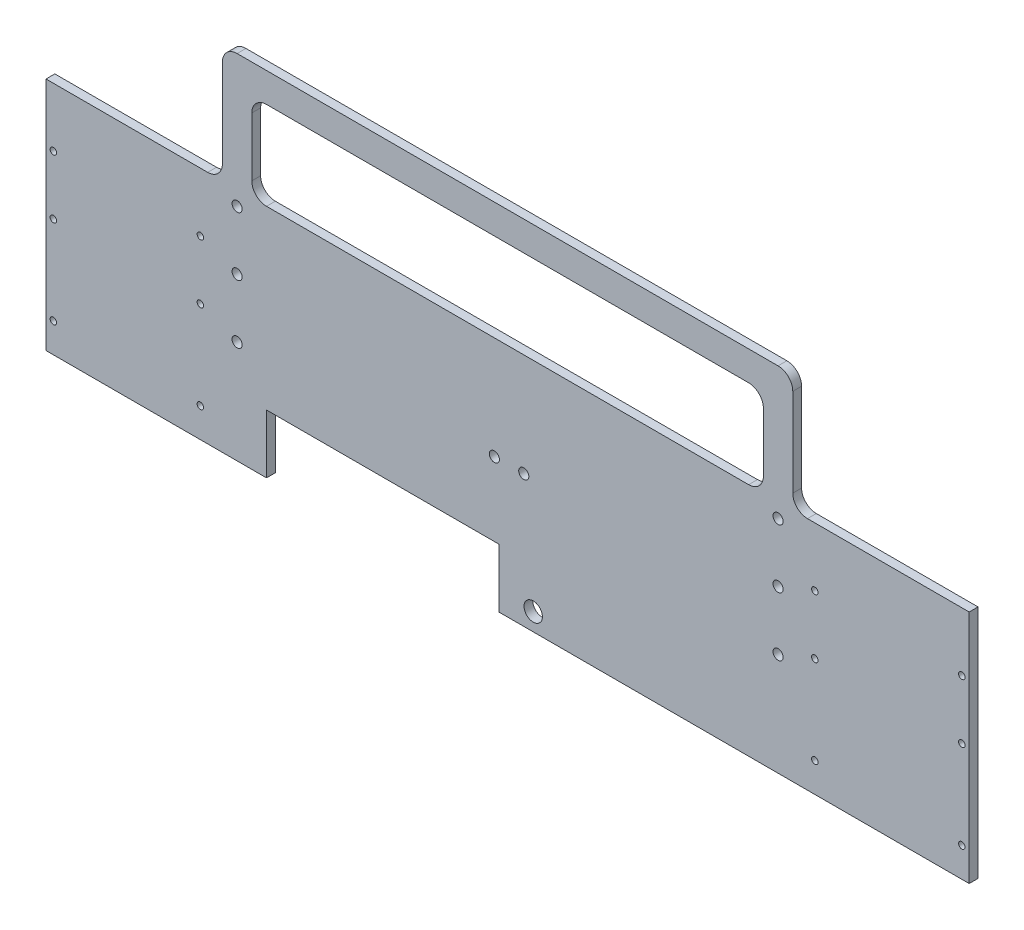
SolidWorks part; units mm, degrees
material "6061-T6 (SS)"
ref_plane "Front Plane" through (0, 0, 0) normal (0, 0, 1) x (1, 0, 0)
ref_plane "Top Plane" through (0, 0, 0) normal (0, 1, 0) x (1, 0, 0)
ref_plane "Right Plane" through (0, 0, 0) normal (1, 0, 0) x (0, 0, -1)
sketch "Sketch1" plane through (0, 0, 0) normal (0, 0, 1) x (1, 0, 0)
  line L1 (-199.39, 50.8) -> (199.39, 50.8)
  line L2 (-199.39, 50.8) -> (-199.39, -50.8)
  line L3 (-199.39, -50.8) -> (199.39, -50.8)
  line L4 (199.39, 50.8) -> (199.39, -50.8)
  line L5 (-199.39, 50.8) -> (199.39, -50.8) construction
  line L6 (-199.39, -50.8) -> (199.39, 50.8) construction
  point P0 (0, 0)
  dimension "D1" = 101.6
  dimension "D2" = 398.78
extrude "Boss-Extrude1" add sketch "Sketch1" along normal blind 3.81
sketch "Sketch2" plane through (0, 0, 3.81) normal (0, 0, 1) x (1, 0, 0)
  line L0 (199.39, -50.8) -> (199.39, 50.8) construction
  line L1 (-91.44, 27.94) -> (91.44, 27.94) construction
  line L2 (-91.44, 27.94) -> (-91.44, -27.94) construction
  line L3 (-91.44, -27.94) -> (91.44, -27.94) construction
  line L4 (91.44, 27.94) -> (91.44, -27.94) construction
  line L5 (-91.44, 27.94) -> (91.44, -27.94) construction
  line L6 (-91.44, -27.94) -> (91.44, 27.94) construction
  line L7 (194.818, -35.56) -> (-194.818, -35.56) construction
  line L8 (194.818, -35.56) -> (194.818, 1.27) construction
  line L9 (194.818, 1.27) -> (-194.818, 1.27) construction
  line L10 (-194.818, -35.56) -> (-194.818, 1.27) construction
  line L11 (194.818, -35.56) -> (-194.818, 1.27) construction
  line L12 (194.818, 1.27) -> (-194.818, -35.56) construction
  line L13 (-199.39, -50.8) -> (199.39, -50.8) construction
  point P0 (0, 0)
  point P6 (0, -17.145)
  point P13 (91.44, 0)
  point P19 (-91.44, 0)
  dimension "D1" = 182.88
  dimension "D2" = 55.88
  dimension "D3" = 4.572
  dimension "D4" = 36.83
  dimension "D5" = 15.24
sketch "Sketch10" plane through (0, 0, 3.81) normal (0, 0, 1) x (1, 0, 0)
  line L0 (199.39, 50.8) -> (-199.39, 50.8) construction
  line L1 (-123.19, 50.8) -> (-110.49, 50.8)
  line L2 (-123.19, 50.8) -> (-123.19, 101.6)
  line L3 (-123.19, 101.6) -> (-114.3, 101.6)
  line L4 (-110.49, 50.8) -> (-110.49, 88.9)
  line L5 (-199.39, 50.8) -> (-199.39, -50.8) construction
  line L6 (-123.19, 101.6) -> (123.19, 101.6)
  line L7 (-123.19, 101.6) -> (-123.19, 96.683)
  line L8 (-110.49, 88.9) -> (110.49, 88.9)
  line L9 (0, 101.6) -> (0, 88.9)
  line L10 (110.49, 50.8) -> (110.49, 88.9)
  line L11 (123.19, 50.8) -> (110.49, 50.8)
  line L12 (123.19, 50.8) -> (123.19, 101.6)
  line M12 (199.39, 50.8) -> (-199.39, 50.8)
  dimension "D1" = 12.7
  dimension "D2" = 12.7
  dimension "D3" = 123.19
  dimension "D4" = 76.2
  dimension "D5" = 50.8
extrude "Boss-Extrude2" add sketch "Sketch10" against normal blind 3.81 contours L9 L6 L3 L2 L4 L8 M12 | L12 L6 L9 L8 L10 M12 region at (-74.645, 89.25, 3.81) region at (74.645, 89.25, 3.81)
fillet "Fillet1" radius 6.35 8 edges at (123.19, 101.6, 1.905) (-123.19, 101.6, 1.905) (-123.19, 50.8, 1.905) (123.19, 50.8, 1.905) (110.49, 88.9, 1.905) (110.49, 50.8, 1.905) (-110.49, 50.8, 1.905) (-110.49, 88.9, 1.905)
sketch "Sketch9" plane through (0, 0, 3.81) normal (0, 0, 1) x (1, 0, 0)
  line L103 (-199.39, -50.8) -> (199.39, -50.8) construction
  point P113 (0, -50.8)
sketch "Sketch11" plane through (0, 0, 3.81) normal (0, 0, 1) x (1, 0, 0)
  line L0 (-199.39, -50.8) -> (199.39, -50.8) construction
  line L1 (-104.14, -50.8) -> (-3.81, -50.8)
  line L2 (-104.14, -50.8) -> (-104.14, -25.4)
  line L3 (-104.14, -25.4) -> (-3.81, -25.4)
  line L4 (-3.81, -50.8) -> (-3.81, -25.4)
  line L5 (-199.39, 50.8) -> (-199.39, -50.8) construction
  line L6 (199.39, -50.8) -> (199.39, 50.8) construction
  dimension "D1" = 25.4
  dimension "D2" = 95.25
  dimension "D3" = 203.2
extrude "Cut-Extrude1" cut sketch "Sketch11" against normal through all
sketch "Sketch12" plane through (0, 0, 3.81) normal (0, 0, 1) x (1, 0, 0)
  line L0 (-3.81, -50.8) -> (-3.81, -25.4) construction
  line L1 (-3.81, -50.8) -> (199.39, -50.8) construction
  point P0 (11.0749, -43.18)
  dimension "D1" = 14.8849
  dimension "D2" = 7.62
hole_wizard "5/16 (0.3125) Diameter Hole1" positions "Sketch13" profile "Sketch14" hole size "5/16" standard "ANSI Inch" end condition through all
sketch "Sketch13" plane through (0, 0, 3.81) normal (0, 0, 1) x (1, 0, 0)
  point P0 (11.0749, -43.18)
sketch "Sketch14" plane through (11.0749, -43.18, 3.81) normal (1, 0, 0) x (0, -1, 0)
  line L0 (0, 0) -> (0, 3.81)
  line L1 (0, 3.81) -> (3.9687, 3.81)
  line L2 (3.9687, 3.81) -> (3.9687, 0)
  line L5 (3.9687, 0) -> (0, 0)
  line L11 (0, -6.35) -> (0, 107.95) construction
  dimension "Thru Hole Dia." = 7.9375
  dimension "Thru Hole Depth" = 3.81
sketch "Sketch15" plane through (0, 0, 3.81) normal (0, 0, 1) x (1, 0, 0)
  line L0 (104.14, 50.8) -> (-104.14, 50.8) construction
  line L1 (-199.39, 50.8) -> (-199.39, -50.8) construction
  line L3 (199.39, -50.8) -> (199.39, 50.8) construction
  point P0 (-116.84, -31.75)
  point P1 (-116.84, -6.35)
  point P2 (-116.84, 19.05)
  point P3 (-116.84, 44.45)
  point P9 (116.84, -31.75)
  point P10 (0, 0)
  point P11 (116.84, -6.35)
  point P12 (116.84, 19.05)
  point P13 (116.84, 44.45)
  point P17 (0, 0)
  dimension "D1" = 82.55
  dimension "D2" = 6.35
  dimension "D3" = 25.4
  dimension "D4" = 25.4
  dimension "D5" = 25.4
  dimension "D6" = 6.35
  dimension "D7" = 25.4
  dimension "D8" = 25.4
  dimension "D9" = 25.4
  dimension "D11" = 82.55
hole_wizard "11/64 (0.17188) Diameter Hole1" positions "Sketch16" profile "Sketch17" hole size "11/64" standard "ANSI Inch" end condition through all
sketch "Sketch16" plane through (0, 0, 3.81) normal (0, 0, 1) x (1, 0, 0)
  point P3 (-116.84, 44.45)
  point P6 (-116.84, 19.05)
  point P15 (116.84, 44.45)
  point P18 (116.84, 19.05)
  point P24 (-116.84, -6.35)
  point P27 (116.84, -6.35)
sketch "Sketch17" plane through (-116.84, 44.45, 3.81) normal (1, 0, 0) x (0, -1, 0)
  line L0 (0, 0) -> (0, 3.81)
  line L1 (0, 3.81) -> (2.1829, 3.81)
  line L2 (2.1829, 3.81) -> (2.1829, 0)
  line L5 (2.1829, 0) -> (0, 0)
  line L11 (0, -6.35) -> (0, 107.95) construction
  dimension "Thru Hole Dia." = 4.3658
  dimension "Thru Hole Depth" = 3.81
sketch "Sketch18" plane through (0, 0, 3.81) normal (0, 0, 1) x (1, 0, 0)
  line L0 (-199.39, 50.8) -> (-199.39, -50.8) construction
  line L1 (-129.54, 50.8) -> (-199.39, 50.8) construction
  line L3 (199.39, -50.8) -> (199.39, 50.8) construction
  line L4 (199.39, 50.8) -> (129.54, 50.8) construction
  line L5 (104.14, 50.8) -> (-104.14, 50.8) construction
  point P0 (-196.215, 25.4)
  point P1 (-196.215, 0)
  point P2 (-196.215, -38.1)
  point P7 (196.215, 25.4)
  point P8 (196.215, 0)
  point P9 (196.215, -38.1)
  point P14 (-132.715, 25.4)
  point P15 (-132.715, 0)
  point P16 (-132.715, -38.1)
  point P19 (132.715, 25.4)
  point P20 (132.715, 0)
  point P21 (132.715, -38.1)
  dimension "D1" = 3.175
  dimension "D2" = 25.4
  dimension "D3" = 25.4
  dimension "D4" = 38.1
  dimension "D5" = 3.175
  dimension "D6" = 25.4
  dimension "D7" = 25.4
  dimension "D8" = 38.1
  dimension "D9" = 66.675
  dimension "D10" = 25.4
  dimension "D11" = 25.4
  dimension "D12" = 38.1
  dimension "D13" = 66.675
  dimension "D14" = 25.4
  dimension "D15" = 25.4
  dimension "D16" = 38.1
hole_wizard "#35 (0.11) Diameter Hole1" positions "Sketch19" profile "Sketch20" hole size "#35" standard "ANSI Inch"
sketch "Sketch19" plane through (0, 0, 3.81) normal (0, 0, 1) x (1, 0, 0)
  point P0 (-196.215, 25.4)
  point P3 (-132.715, 25.4)
  point P6 (-132.715, 0)
  point P9 (-196.215, 0)
  point P12 (-196.215, -38.1)
  point P15 (-132.715, -38.1)
  point P18 (132.715, -38.1)
  point P21 (196.215, -38.1)
  point P24 (196.215, 0)
  point P27 (196.215, 25.4)
  point P30 (132.715, 25.4)
  point P33 (132.715, 0)
sketch "Sketch20" plane through (-196.215, 25.4, 3.81) normal (1, 0, 0) x (0, -1, 0)
  line L0 (0, 0) -> (0, 9.7294)
  line L1 (0, 9.7294) -> (1.397, 8.89)
  line L2 (1.397, 8.89) -> (1.397, 0)
  line L5 (1.397, 0) -> (0, 0)
  line L10 (0, 9.7294) -> (-1.397, 8.89) construction
  line L11 (0, -6.35) -> (0, 107.95) construction
  dimension "Hole Dia." = 2.794
  dimension "Hole Depth" = 8.89
  dimension "Drill Angle" = 118
sketch "Sketch21" plane through (0, 0, 3.81) normal (0, 0, 1) x (1, 0, 0)
  line L0 (104.14, 50.8) -> (-104.14, 50.8) construction
  line L1 (-199.39, 50.8) -> (-199.39, -50.8) construction
  point P0 (-5.715, 6.35)
  point P5 (6.985, 6.35)
  dimension "D1" = 44.45
  dimension "D2" = 193.675
  dimension "D3" = 44.45
  dimension "D4" = 206.375
hole_wizard "11/64 (0.17188) Diameter Hole2" positions "Sketch22" profile "Sketch23" hole size "11/64" standard "ANSI Inch"
sketch "Sketch22" plane through (0, 0, 3.81) normal (0, 0, 1) x (1, 0, 0)
  point P0 (-5.715, 6.35)
  point P3 (6.985, 6.35)
sketch "Sketch23" plane through (-5.715, 6.35, 3.81) normal (1, 0, 0) x (0, -1, 0)
  line L0 (0, 0) -> (0, 10.2016)
  line L1 (0, 10.2016) -> (2.1829, 8.89)
  line L2 (2.1829, 8.89) -> (2.1829, 0)
  line L5 (2.1829, 0) -> (0, 0)
  line L10 (0, 10.2016) -> (-2.1829, 8.89) construction
  line L11 (0, -6.35) -> (0, 107.95) construction
  dimension "Hole Dia." = 4.3658
  dimension "Hole Depth" = 8.89
  dimension "Drill Angle" = 118
